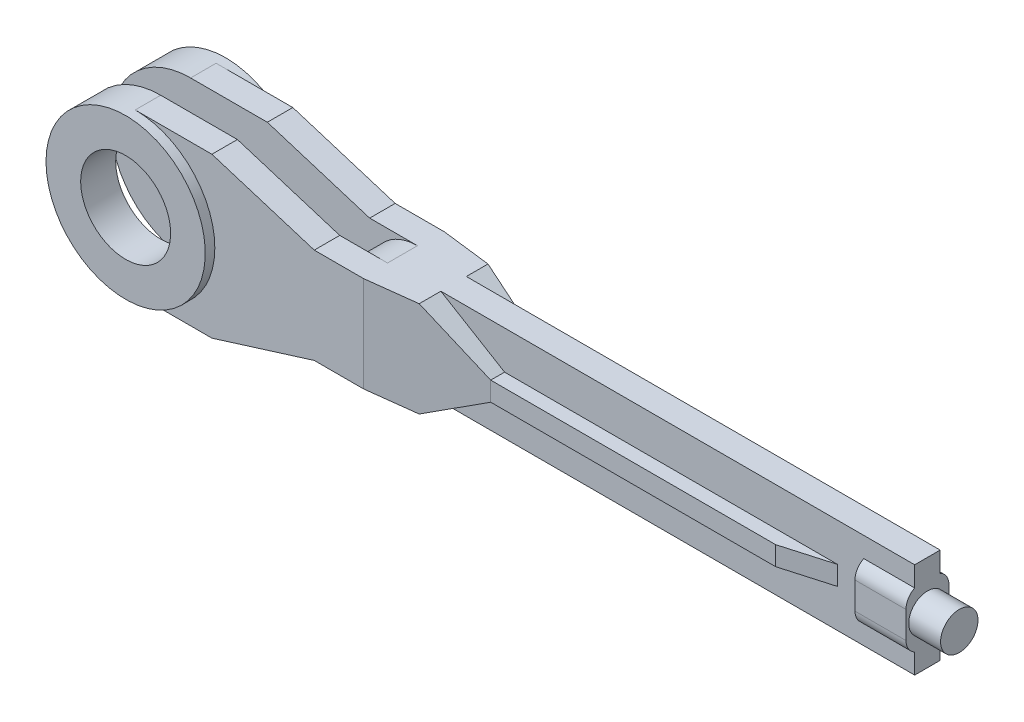
SolidWorks part; units mm, degrees
ref_plane "Front Plane" through (0, 0, 0) normal (0, 0, 1) x (1, 0, 0)
ref_plane "Top Plane" through (0, 0, 0) normal (0, 1, 0) x (1, 0, 0)
ref_plane "Right Plane" through (0, 0, 0) normal (1, 0, 0) x (0, 0, -1)
sketch "Sketch1" plane through (0, 0, 0) normal (0, 0, 1) x (1, 0, 0)
  line L0 (0, 12.5) -> (12.0413, 12.5)
  line L1 (12.0413, 12.5) -> (28.1062, 7.5)
  line L5 (28.1062, -7.5) -> (12.0413, -12.5)
  line L6 (12.0413, -12.5) -> (0, -12.5)
  line L7 (0, 0) -> (28.1062, 0) construction
  line L8 (28.1062, 7.5) -> (28.1062, -7.5)
  circle A0 centre (0, 0) radius 7.0625
  arc A1 (0, 12.5) -> (0, -12.5) centre (0, 0) ccw
  dimension "D1" = 14.125
  dimension "D2" = 25
  dimension "D3" = 15
extrude "Boss-Extrude1" add sketch "Sketch1" along normal blind 4
ref_plane "Plane1" through (0, 0, -2.35) normal (0, 0, -1) x (-1, 0, 0)
sketch "Sketch5" plane through (0, 0, 4) normal (0, 0, 1) x (1, 0, 0)
  line L0 (28.1062, 7.5) -> (28.1062, -7.5)
  line L1 (28.1062, 7.5) -> (53.6281, 7.5)
  line L3 (28.1062, -7.5) -> (53.6281, -7.5)
  line L4 (53.6281, 7.5) -> (53.6281, -7.5)
extrude "Boss-Extrude2" add sketch "Sketch5" against normal blind 12.7
mirror "Mirror1" about plane through (0, 0, -2.35) normal (0, 0, -1) of "Boss-Extrude1"
fillet "Fillet1" radius 7.5 2 edges at (28.1062, -7.5, -2.35) (28.1062, 7.5, -2.35)
sketch "Sketch6" plane through (0, 0, -2.35) normal (0, 0, -1) x (-1, 0, 0)
  line L0 (-28.1062, -7.5) -> (-53.6281, -7.5) construction
  line L1 (-53.6281, 7.5) -> (-118, 7.5)
  line L2 (-53.6281, 7.5) -> (-53.6281, -7.5)
  line L3 (-53.6281, -7.5) -> (-118, -7.5)
  line L4 (-118, 7.5) -> (-118, -7.5)
  point P8 (-118, 0)
  dimension "D1" = 118
extrude "Boss-Extrude3" add sketch "Sketch6" along normal mid plane 4
chamfer "Chamfer1" distance 10 distance2 6 2 edges at (53.6281, 7.5, 1.825) (53.6281, 7.5, -6.525) first distance on face at (52.8458, 7.5, -2.35)
chamfer "Chamfer2" distance 6 distance2 10 2 edges at (53.6281, -7.5, 1.825) (53.6281, -7.5, -6.525) first distance on face at (53.6281, -3, 1.825) first distance on face at (53.6281, -3, -6.525)
sketch "Sketch8" plane through (118, 0, 0) normal (1, 0, 0) x (0, 0, -1)
  line L0 (2.35, -16.9531) -> (2.35, 16.9531) construction
  circle A0 centre (2.35, 0) radius 2.9375
  dimension "D1" = 5.875
extrude "Boss-Extrude4" add sketch "Sketch8" along normal blind 5
sketch "Sketch9" plane through (0, 0, 0) normal (0, 1, 0) x (1, 0, 0)
  line L0 (53.6281, 8.7) -> (53.6281, 4.35) construction
  line L1 (53.6281, 6.525) -> (98.3499, 6.525)
  line L2 (53.6281, 6.525) -> (53.6281, -1.825)
  line L3 (53.6281, -1.825) -> (98.3499, -1.825)
  line L5 (92.9263, 2.35) -> (50092.9263, 2.35) construction
  line L6 (16.9531, 2.35) -> (-16.9531, 2.35) construction
  line L7 (98.3499, 6.525) -> (112.8561, 2.35)
  line L8 (112.8561, 2.35) -> (98.3499, -1.825)
  point P9 (100.562, 6.525)
  point P10 (98.3499, 6.525)
  point P11 (112.8561, 2.35)
extrude "Boss-Extrude5" add sketch "Sketch9" along normal mid plane 3
sketch "Sketch10" plane through (0, 0, 0) normal (0, 1, 0) x (1, 0, 0)
  line L0 (53.6281, 6.525) -> (35.8429, 8.7)
  line L1 (35.8429, 8.7) -> (53.6281, 8.7)
  line L2 (43.6281, 8.7) -> (53.6281, 8.7) construction
  line L3 (53.6281, 8.7) -> (53.6281, 6.525)
  line L4 (53.6281, -1.825) -> (35.8429, -4)
  line L5 (35.8429, -4) -> (53.6281, -4)
  line L6 (53.6281, -4) -> (53.6281, -1.825)
  point P13 (43.6281, 8.7)
  point P14 (43.6281, 8.7)
extrude "Cut-Extrude1" cut sketch "Sketch10" against normal mid plane 15
sketch "Sketch11" plane through (118, 0, 0) normal (-1, 0, 0) x (0, 0, 1)
  line L5 (-5.7213, -4.3444) -> (1.0213, -4.3444)
  line L6 (-5.7213, -4.3444) -> (-5.7213, 4.3444)
  line L7 (-5.7213, 4.3444) -> (1.0213, 4.3444)
  line L8 (1.0213, -4.3444) -> (1.0213, 4.3444)
extrude "Boss-Extrude7" add sketch "Sketch11" along normal blind 8
fillet "Fillet2" radius 2.5 4 edges at (114, 4.3444, 1.0213) (114, -4.3444, 1.0213) (114, 4.3444, -5.7213) (114, -4.3444, -5.7213)
sketch "Sketch12" plane through (0, 0, -8.7) normal (0, 0, -1) x (-1, 0, 0)
  circle A0 centre (0, 0) radius 7.0625 construction
  circle A1 centre (0, 0) radius 7.0625
  circle A2 centre (0, 0) radius 12.5
extrude "Boss-Extrude8" add sketch "Sketch12" along normal blind 1.5
mirror "Mirror2" about plane through (0, 0, -2.35) normal (0, 0, -1) of "Boss-Extrude8"
